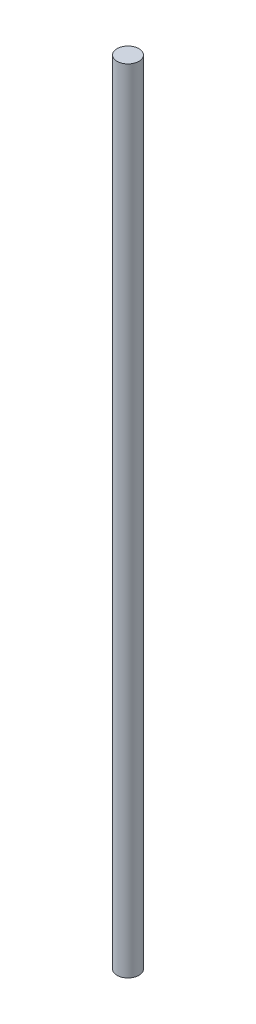
SolidWorks part; units mm, degrees
ref_plane "Front Plane" through (0, 0, 0) normal (0, 0, 1) x (1, 0, 0)
ref_plane "Top Plane" through (0, 0, 0) normal (0, 1, 0) x (1, 0, 0)
ref_plane "Right Plane" through (0, 0, 0) normal (1, 0, 0) x (0, 0, -1)
sketch "Sketch1" plane through (0, 0, 0) normal (0, 1, 0) x (1, 0, 0)
  circle A0 centre (0, 0) radius 2.5
  dimension "D1" = 5
extrude "Body" add sketch "Sketch1" along normal blind 180.5
